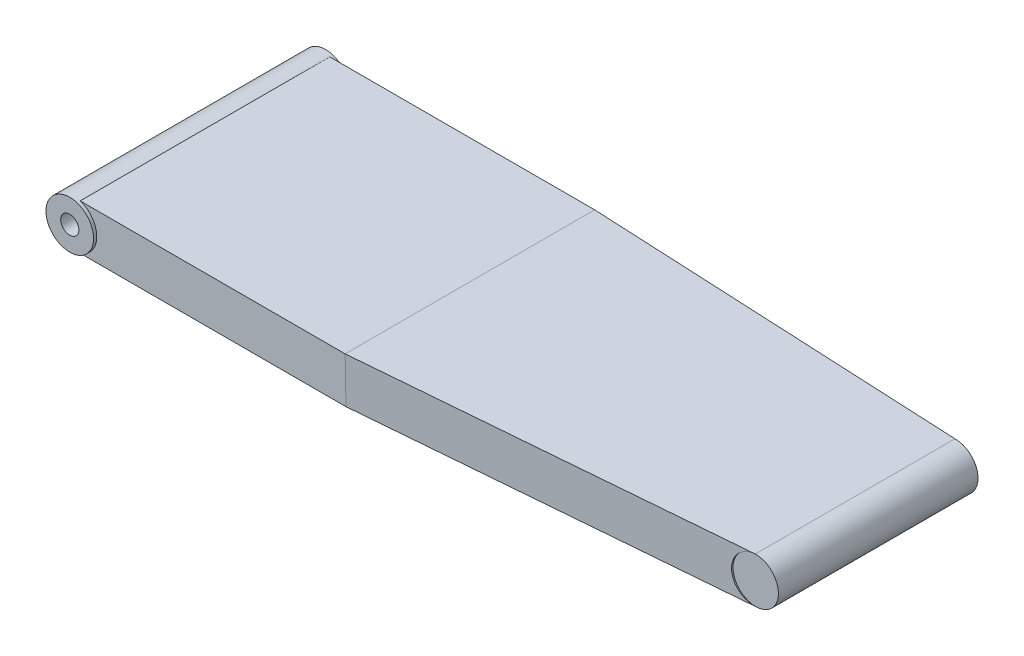
SolidWorks part; units mm, degrees
material "PA Tipo 6"
ref_plane "Plano frontal" through (0, 0, 0) normal (0, 0, 1) x (1, 0, 0)
ref_plane "Plano superior" through (0, 0, 0) normal (0, 1, 0) x (1, 0, 0)
ref_plane "Plano direito" through (0, 0, 0) normal (1, 0, 0) x (0, 0, -1)
sketch "Esboço1" plane through (0, 0, 0) normal (0, 0, 1) x (1, 0, 0)
  line L0 (1.5983, 5.0008) -> (60, 5.0008)
  line L1 (1.5983, -5.0008) -> (60, -5.0008)
  line L2 (60, -5.0008) -> (145.0883, -3.4984)
  line L3 (60, 5.0008) -> (144.9117, 6.5)
  line L4 (60, 5.0008) -> (60, -5.0008)
  circle A0 centre (0, 0) radius 5.25
  circle A1 centre (145, 1.5008) radius 5
  dimension "D1" = 10.5
  dimension "D2" = 10
  dimension "D3" = 3.5
  dimension "D5" = 145
  dimension "D6" = 85
extrude "Ressalto-extrusão1" add sketch "Esboço1" along normal mid plane 56.4 contours A0 region at (0, 0, 0)
extrude "Ressalto-extrusão3" add sketch "Esboço1<5>" along normal mid plane 44 separate body contours A1 region at (145, 1.5008, 0)
sketch "Esboço1<5>" plane through (0, 0, 0) normal (0, 0, 1) x (1, 0, 0) same geometry as "Esboço1"
extrude "Ressalto-extrusão4" add sketch "Esboço1<7>" along normal mid plane 55 contours A0 L1 L4 L0 region at (32.1292, 0, 0)
sketch "Esboço1<7>" plane through (0, 0, 0) normal (0, 0, 1) x (1, 0, 0) same geometry as "Esboço1"
extrude "Ressalto-extrusão5" add sketch "Esboço1<8>" along normal mid plane 55 contours A1 L3 L4 L2 region at (100.5445, 0.714, 0)
sketch "Esboço1<8>" plane through (0, 0, 0) normal (0, 0, 1) x (1, 0, 0) same geometry as "Esboço1"
sketch "Esboço2" plane through (-0.0696, 3.9402, 0) normal (-0.0177, 0.9998, 0) x (0.9998, 0.0177, 0)
  line L0 (60.0789, -27.5) -> (145.0039, -22)
  line L2 (160.1659, 0) -> (-10.8244, 0) construction
  line L3 (60.0789, 27.5) -> (145.0039, 22)
  line L4 (145.0039, 22) -> (145.0039, 27.5)
  line L5 (145.0039, 27.5) -> (60.0789, 27.5)
  line L6 (145.0039, -22) -> (145.0039, -27.5)
  line L7 (145.0039, -27.5) -> (60.0789, -27.5)
extrude "Corte-extrusão3" cut sketch "Esboço2" against normal through all
sketch "Esboço3" plane through (0, 0, 28.2) normal (0, 0, 1) x (1, 0, 0)
  circle A0 centre (0, 0) radius 2
  dimension "D1" = 4
extrude "Corte-extrusão4" cut sketch "Esboço3" against normal through all
